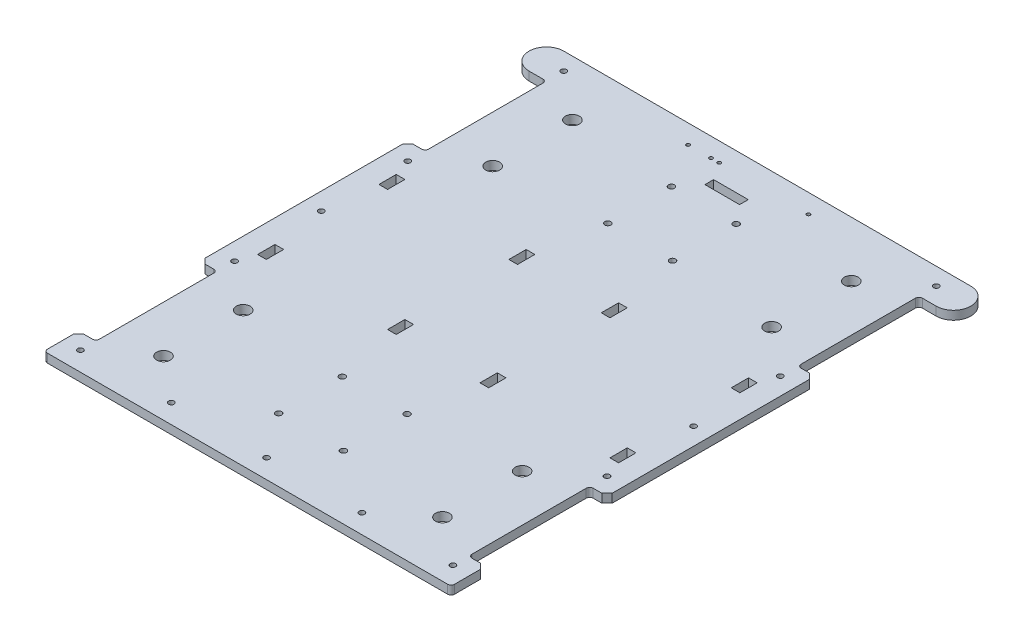
SolidWorks part; units mm, degrees
material "Teak"
ref_plane "Front Plane" through (0, 0, 0) normal (0, 0, 1) x (1, 0, 0)
ref_plane "Top Plane" through (0, 0, 0) normal (0, 1, 0) x (1, 0, 0)
ref_plane "Right Plane" through (0, 0, 0) normal (1, 0, 0) x (0, 0, -1)
sketch "Sketch1" plane through (0, 0, 0) normal (0, 1, 0) x (1, 0, 0)
  line L0 (0, 170) -> (0, -130) construction
  line L1 (-117.5, 0) -> (117.5, 0) construction
  line L2 (-117.5, -130) -> (117.5, -130)
  line L3 (117.5, -130) -> (117.5, -110)
  line L4 (117.5, -110) -> (107.5, -110)
  line L5 (107.5, -110) -> (107.5, -40)
  line L6 (107.5, -40) -> (117.5, -40)
  line L7 (117.5, -40) -> (117.5, 80)
  line L8 (117.5, 80) -> (107.5, 80)
  line L9 (107.5, 80) -> (107.5, 150)
  line L10 (107.5, 150) -> (127.5, 150)
  line L11 (-107.5, 150) -> (-127.5, 150)
  line L12 (-107.5, 80) -> (-107.5, 150)
  line L13 (-117.5, 80) -> (-107.5, 80)
  line L14 (-117.5, -40) -> (-117.5, 80)
  line L15 (-107.5, -40) -> (-117.5, -40)
  line L16 (-107.5, -110) -> (-107.5, -40)
  line L17 (-117.5, -110) -> (-107.5, -110)
  line L18 (-117.5, -130) -> (-117.5, -110)
  line L19 (127.5, 150) -> (127.5, 170)
  line L20 (127.5, 170) -> (-127.5, 170)
  line L21 (-127.5, 150) -> (-127.5, 170)
  point P5 (0, 0)
  dimension "D1" = 300
  dimension "D2" = 20
  dimension "D3" = 20
  dimension "D5" = 10
  dimension "D6" = 70
  dimension "D7" = 70
  dimension "D8" = 255
  dimension "D9" = 20
extrude "Boss-Extrude1" add sketch "Sketch1" along normal blind 5
fillet "Fillet3" 2 edges at (127.5, 2.5, -150) (127.5, 2.5, -170) type full round first side face at (117.5, 2.5, -150) second side face at (0, 2.5, -170) middle face at (127.5, 2.5, -160)
fillet "Fillet4" 2 edges at (-127.5, 2.5, -170) (-127.5, 2.5, -150) type full round first side face at (-5, 2.5, -170) second side face at (-117.5, 2.5, -150) middle face at (-127.5, 2.5, -160)
fillet "Fillet2" radius 2 10 edges at (107.5, 2.5, 40) (107.5, 2.5, -150) (107.5, 2.5, -80) (107.5, 2.5, 110) (-107.5, 2.5, -80) (-107.5, 2.5, 110) (-107.5, 2.5, 40) (-107.5, 2.5, -150) (-117.5, 2.5, 130) (117.5, 2.5, 130)
sketch "Sketch2" plane through (0, 5, 0) normal (0, 1, 0) x (1, 0, 0)
  line L0 (0, -130) -> (0, 90) construction
  line L1 (-115.5, -130) -> (115.5, -130) construction
  line L2 (107.5, 82) -> (107.5, 148) construction
  line L4 (117.5, -40) -> (117.5, 80) construction
  line L5 (117.5, -128) -> (117.5, -110) construction
  arc A0 (117.5, 150) -> (117.5, 170) centre (117.5, 160) ccw construction
  circle A1 centre (107.5, 160) radius 1.6
  circle A2 centre (107.5, 20) radius 1.6
  circle A3 centre (107.5, -119) radius 1.6
  circle A4 centre (0, -119) radius 1.6
  circle A5 centre (-107.5, -119) radius 1.6
  circle A6 centre (-107.5, 20) radius 1.6
  circle A7 centre (-107.5, 160) radius 1.6
  circle A8 centre (55, -119) radius 1.6
  circle A9 centre (-55, -119) radius 1.6
  circle A10 centre (-107.5, 70) radius 1.6
  circle A11 centre (107.5, 70) radius 1.6
  circle A12 centre (-107.5, -30) radius 1.6
  circle A13 centre (107.5, -30) radius 1.6
  point P17 (127.5, 160)
  point P26 (117.5, 20)
  point P30 (117.5, -119)
  dimension "D1" = 3.2
  dimension "D2" = 2
  dimension "D3" = 10
  dimension "D4" = 2
  dimension "D5" = 2
  dimension "D6" = 2
  dimension "D7" = 2
extrude "layer fix hole" cut sketch "Sketch2" against normal through all
chamfer "Chamfer1" distance 3 angle 45 6 edges at (117.5, 2.5, 110) (-117.5, 2.5, -80) (-117.5, 2.5, 40) (-117.5, 2.5, 110) (117.5, 2.5, -80) (117.5, 2.5, 40)
sketch "Sketch9" plane through (0, 0, 0) normal (0, -1, 0) x (1, 0, 0)
  line L0 (107.5, -115) -> (-119.4618, -115) construction
  line L1 (107.5, -82) -> (107.5, -148) construction
  line L2 (107.5, 75) -> (-117.246, 75) construction
  line L3 (107.5, 108) -> (107.5, 42) construction
  line L4 (-117.5, -20) -> (128.0189, -20) construction
  line L5 (0, 75) -> (0, -115) construction
  line L6 (-80.5, -96.3983) -> (-80.5, -133.6017) construction
  line L7 (-107.5, -148) -> (-107.5, -82) construction
  line L8 (-117.5, -77) -> (-117.5, 37) construction
  circle A0 centre (-80.5, -138) radius 4
  circle A1 centre (-80.5, -92) radius 4
  circle A2 centre (80.5, -92) radius 4
  circle A3 centre (80.5, -138) radius 4
  circle A4 centre (80.5, 98) radius 4
  circle A5 centre (80.5, 52) radius 4
  circle A6 centre (-80.5, 98) radius 4
  circle A7 centre (-80.5, 52) radius 4
  point P16 (-80.5, -115)
  dimension "D2" = 8
  dimension "D1" = 27
  dimension "D3" = 23
extrude "Motor fix hole" cut sketch "Sketch9" against normal up to next
sketch "Sketch10" plane through (0, 0, 0) normal (0, -1, 0) x (1, 0, 0)
  line L0 (-117.5, -20) -> (130.9103, -20) construction
  line L1 (-117.5, -77) -> (-117.5, 37) construction
  line L2 (0, 130) -> (0, -170) construction
  line L3 (-115.5, 130) -> (115.5, 130) construction
  line L4 (117.5, -170) -> (-117.5, -170) construction
  line L5 (-18.6898, 56.6291) -> (18.6898, 56.6291) construction
  line L6 (-23.6898, 98.3709) -> (23.6898, 98.3709) construction
  line L7 (-23.6898, 98.3709) -> (-23.6898, 51.6291) construction
  line L8 (-23.6898, 51.6291) -> (23.6898, 51.6291) construction
  line L9 (23.6898, 98.3709) -> (23.6898, 51.6291) construction
  line L10 (-23.6898, 98.3709) -> (23.6898, 51.6291) construction
  line L11 (-23.6898, 51.6291) -> (23.6898, 98.3709) construction
  line L12 (18.6898, 93.3709) -> (18.6898, 56.6291) construction
  line L13 (-18.6898, 93.3709) -> (18.6898, 93.3709) construction
  line L14 (-18.6898, 93.3709) -> (-18.6898, 56.6291) construction
  line L18 (-18.6898, -133.3709) -> (-18.6898, -96.6291) construction
  line L19 (-18.6898, -133.3709) -> (18.6898, -133.3709) construction
  line L25 (18.6898, -133.3709) -> (18.6898, -96.6291) construction
  line L28 (-23.6898, -91.6291) -> (23.6898, -138.3709) construction
  line L29 (-107.5, 75) -> (107.5, 75) construction
  line L30 (-23.6898, -138.3709) -> (23.6898, -91.6291) construction
  line L32 (23.6898, -138.3709) -> (23.6898, -91.6291) construction
  line L33 (-23.6898, -91.6291) -> (23.6898, -91.6291) construction
  line L34 (-23.6898, -138.3709) -> (-23.6898, -91.6291) construction
  line L35 (-107.5, 42) -> (-107.5, 108) construction
  line L36 (-23.6898, -138.3709) -> (23.6898, -138.3709) construction
  line L37 (-18.6898, -96.6291) -> (18.6898, -96.6291) construction
  line L38 (107.5, 108) -> (107.5, 42) construction
  circle A0 centre (18.6898, 56.6291) radius 1.75
  circle A1 centre (-18.6898, 56.6291) radius 1.75
  circle A2 centre (-18.6898, 93.3709) radius 1.75
  circle A3 centre (18.6898, 93.3709) radius 1.75
  circle A4 centre (18.6898, -133.3709) radius 1.75
  circle A5 centre (-18.6898, -133.3709) radius 1.75
  circle A6 centre (-18.6898, -96.6291) radius 1.75
  circle A7 centre (18.6898, -96.6291) radius 1.75
  point P10 (0, 75)
  point P37 (0, -115)
  dimension "D3" = 3.5
  dimension "D1" = 37.3795
  dimension "D2" = 5
  dimension "D4" = 36.7418
extrude "Motor driver fix hole" cut sketch "Sketch10" against normal up to next
sketch "Sketch11" plane through (0, 0, 0) normal (0, -1, 0) x (1, 0, 0)
  line L0 (0, -170) -> (0, -144.1108) construction
  line L1 (117.5, -170) -> (-117.5, -170) construction
  line L2 (0, -144.1108) -> (0, -110.0028) construction
  line L5 (-37.465, -159) -> (37.465, -159) construction
  line L7 (34.2319, -158.1371) -> (37.465, -159) construction
  line L8 (-37.465, -159) -> (-34.2319, -158.1371) construction
  line L10 (-10, -144) -> (10, -144)
  line L11 (-10, -144) -> (-10, -149)
  line L12 (-10, -149) -> (10, -149)
  line L13 (10, -144) -> (10, -149)
  line L14 (-10, -144) -> (10, -149) construction
  line L15 (-10, -149) -> (10, -144) construction
  circle A0 centre (-34.7373, -159) radius 1
  circle A1 centre (-21.5138, -159) radius 1
  circle A2 centre (-16.8148, -159) radius 1
  circle A3 centre (34.7373, -159) radius 1
  point P1 (0, -146.5)
  point P5 (0, -149.001)
  dimension "D2" = 2.7277
  dimension "D6" = 2
  dimension "D1" = 2.7277
  dimension "D3" = 13.2235
  dimension "D4" = 4.699
  dimension "D5" = 51.5521
  dimension "D7" = 20
  dimension "D8" = 5
  dimension "D9" = 11
  dimension "D10" = 10
extrude "QTR8a fix hole" cut sketch "Sketch11" against normal blind 10
sketch "Sketch 12" plane through (0, 5, 0) normal (0, 1, 0) x (1, 0, 0)
  line L0 (-39.1667, 170) -> (-39.1667, -135.4982) construction
  line L1 (117.5, 170) -> (-117.5, 170) construction
  line L2 (-117.5, 20) -> (117.5, 20) construction
  line L12 (24.1667, 60) -> (29.1667, 60)
  line L37 (-117.5, -120.5) -> (-39.1667, -120.5) construction
  line L38 (39.1667, 170) -> (39.1667, -135.4982) construction
  line L39 (-39.1667, -120.5) -> (39.1667, -120.5) construction
  line L40 (39.1667, -120.5) -> (117.5, -120.5) construction
  line L41 (117.5, -128) -> (117.5, -113) construction
  line L42 (-117.5, -113) -> (-117.5, -128) construction
  line L43 (99.1667, 60) -> (99.1667, 50)
  line L44 (24.1667, 60) -> (24.1667, 50)
  line L45 (24.1667, 50) -> (29.1667, 50)
  line L46 (29.1667, 60) -> (29.1667, 50)
  line L86 (-117.5, 77) -> (-117.5, -37) construction
  line L87 (117.5, -37) -> (117.5, 77) construction
  line L88 (24.1667, -10) -> (29.1667, -10)
  line L89 (29.1667, -20) -> (29.1667, -10)
  line L90 (24.1667, -20) -> (29.1667, -20)
  line L91 (24.1667, -20) -> (24.1667, -10)
  line L92 (99.1667, 60) -> (104.1667, 60)
  line L93 (104.1667, 60) -> (104.1667, 50)
  line L94 (99.1667, 50) -> (104.1667, 50)
  line L95 (99.1667, -10) -> (104.1667, -10)
  line L96 (104.1667, -20) -> (104.1667, -10)
  line L97 (99.1667, -20) -> (104.1667, -20)
  line L98 (99.1667, -20) -> (99.1667, -10)
  line L99 (-104.1667, 60) -> (-99.1667, 60)
  line L100 (-29.1667, 60) -> (-29.1667, 50)
  line L101 (-104.1667, 60) -> (-104.1667, 50)
  line L102 (-104.1667, 50) -> (-99.1667, 50)
  line L103 (-99.1667, 60) -> (-99.1667, 50)
  line L104 (-104.1667, -10) -> (-99.1667, -10)
  line L105 (-99.1667, -20) -> (-99.1667, -10)
  line L106 (-104.1667, -20) -> (-99.1667, -20)
  line L107 (-104.1667, -20) -> (-104.1667, -10)
  line L108 (-29.1667, 60) -> (-24.1667, 60)
  line L109 (-24.1667, 60) -> (-24.1667, 50)
  line L110 (-29.1667, 50) -> (-24.1667, 50)
  line L111 (-29.1667, -10) -> (-24.1667, -10)
  line L112 (-24.1667, -20) -> (-24.1667, -10)
  line L113 (-29.1667, -20) -> (-24.1667, -20)
  line L114 (-29.1667, -20) -> (-29.1667, -10)
  line L115 (-245.8333, 20) -> (-10.8333, 20) construction
  line L117 (-89.1667, 170) -> (-89.1667, -135.4982) construction
  point P0 (29.1667, 55)
  dimension "D1" = 5
  dimension "D2" = 10
  dimension "D3" = 10
  dimension "D4" = 2
  dimension "D7" = 60
  dimension "D8" = 10
  dimension "D5" = 2
  dimension "D6" = 70
extrude "Battery fixed hole" cut sketch "Sketch 12" against normal through all
sketch "Sketch12" plane through (0, 5, 0) normal (0, 1, 0) x (1, 0, 0)
